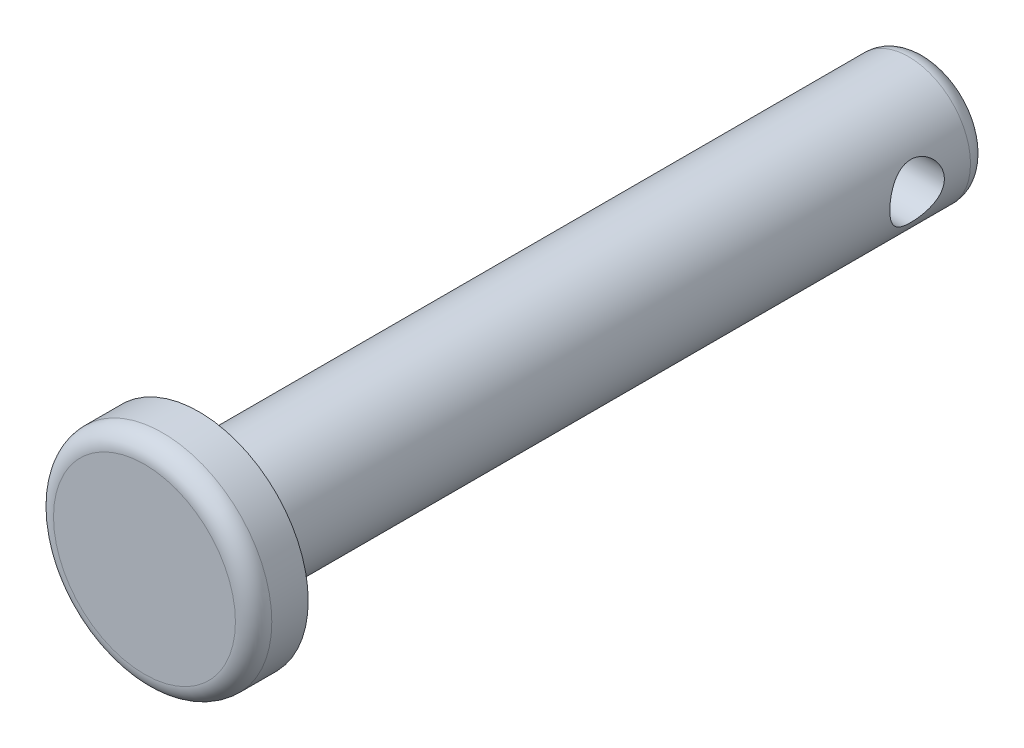
SolidWorks part; units mm, degrees
material "1060 Alloy"
ref_plane "Front Plane" through (0, 0, 0) normal (0, 0, 1) x (1, 0, 0)
ref_plane "Top Plane" through (0, 0, 0) normal (0, 1, 0) x (1, 0, 0)
ref_plane "Right Plane" through (0, 0, 0) normal (1, 0, 0) x (0, 0, -1)
other "Configuration Table"
sketch "Sketch4" plane through (0, 0, 0) normal (1, 0, 0) x (0, 0, -1)
  line L0 (0, -8.7623) -> (0, 8.2377)
  line L1 (0, 8.2377) -> (-200.0284, 8.2377)
  line L2 (-200.0284, 8.2377) -> (-200.0284, 21.2377)
  line L3 (-200.0284, 21.2377) -> (-215.0284, 21.2377)
  line L4 (-215.0284, 21.2377) -> (-215.0284, -8.7623)
  line L6 (-221.5211, -8.7623) -> (8.5013, -8.7623) construction
  dimension "D1" = 200.0284
  dimension "D2" = 215.0284
  dimension "D3" = 8.2377
  dimension "D4" = 21.2377
  dimension "D5" = 8.7623
revolve "Revolve1" add sketch "Sketch4" angle 360 about L6 region at (0, 0.4973, 112.5792)
fillet "Fillet2" radius 5 1 edges at (17, -8.7623, 0)
fillet "Fillet3" radius 5 1 edges at (30, -8.7623, 215.0284)
sketch "Sketch5" plane through (0, 0, 0) normal (1, 0, 0) x (0, 0, -1)
  line L0 (-221.5211, -8.7623) -> (8.5013, -8.7623) construction
  circle A0 centre (-19.6796, -8.7623) radius 7.5
  dimension "D1" = 15
  dimension "D2" = 19.6796
extrude "Cut-Extrude1" cut sketch "Sketch5" against normal blind 20 and the other way blind 20
